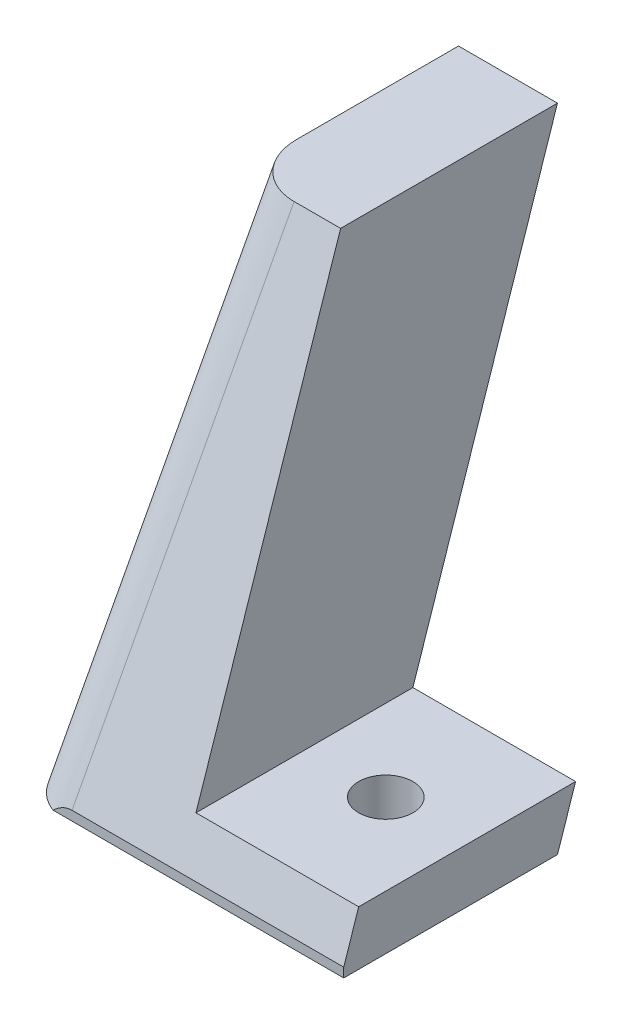
SolidWorks part; units mm, degrees
ref_plane "Спереди" through (0, 0, 0) normal (0, 0, 1) x (1, 0, 0)
ref_plane "Сверху" through (0, 0, 0) normal (0, 1, 0) x (1, 0, 0)
ref_plane "Справа" through (0, 0, 0) normal (1, 0, 0) x (0, 0, -1)
sketch "Эскиз1" plane through (0, 0, 0) normal (0, 1, 0) x (1, 0, 0)
  line L1 (-82.6594, 0) -> (83.4888, 0) construction
  line L3 (-45, 0) -> (-45, 45)
  line L4 (-45, 45) -> (45, 45)
  line L5 (45, 45) -> (45, -45)
  line L6 (45, -45) -> (-45, -45)
  line L7 (-45, -45) -> (-45, 0)
  dimension "D1" = 90
  dimension "D2" = 90
  dimension "D4" = 45
sketch "Эскиз2" plane through (0, 0, 0) normal (0, 0, 1) x (1, 0, 0)
  line L0 (-45, 0) -> (-30, 0)
  line L1 (-30, 0) -> (-30, 45)
  line L2 (45, 0) -> (-45, 0) construction
  line L4 (-45, 0) -> (-30, 0)
  line L5 (0, 0) -> (0, 57.5371) construction
  line L6 (-39.125, 45) -> (-30, 45)
  line L7 (0, 45) -> (-39.125, 45)
  line L8 (-39.125, 45) -> (-45, 0)
  dimension "D1" = 45
  dimension "D2" = 39.125
  dimension "D3" = 82.562
  dimension "D4" = 15
  dimension "D5" = 45
extrude "Бобышка-Вытянуть1" add sketch "Эскиз2" along normal blind 50 contours L6 L8 L0 L1 region at (-36.1505, 20.6736, 0)
sketch "Эскиз4" plane through (0, 0, 0) normal (1, 0, 0) x (0, 0, -1)
  line L0 (-50.289, 0) -> (-50, 45)
  line L2 (-50, 45) -> (-35.289, 45)
  line L3 (-15.2933, 45) -> (-35.289, 45)
  line L4 (-50.289, 0) -> (-35.289, 45)
  line L5 (-50.289, 0) -> (-30.289, 0)
  line L6 (-30.289, 0) -> (-15.2933, 45)
  line L7 (-15.2933, 45) -> (0, 45)
  line L8 (0, 45) -> (0, 0)
  line L9 (0, 0) -> (-30.289, 0)
  dimension "D1" = 71.565
  dimension "D2" = 71.57
  dimension "D3" = 19.9957
  dimension "D4" = 45
  dimension "D5" = 20
  dimension "D6" = 30.289
  dimension "D7" = 50.289
extrude "Вырез-Вытянуть1" cut sketch "Эскиз4" against normal blind 50 contours L7 L8 L9 L6 | L4 L2 L0
sketch "Эскиз7" plane through (-30, 0, 0) normal (1, 0, 0) x (0, 0, -1)
  line L0 (-50, 0) -> (-50, 0.8669)
  line L1 (-50, 0.8669) -> (-48.6223, 5)
  line L2 (-48.6223, 5) -> (-28.6228, 5)
  line L3 (-35.289, 45) -> (-50, 0.8669) construction
  line L4 (-15.2933, 45) -> (-30.289, 0) construction
  line L6 (-28.6228, 5) -> (-30.289, 0)
  line L7 (-30.289, 0) -> (-50, 0)
  dimension "D1" = 5
extrude "Бобышка-Вытянуть3" add sketch "Эскиз7" along normal blind 15
sketch "Эскиз8" plane through (0, 5, 0) normal (0, 1, 0) x (1, 0, 0)
  line L0 (-15, -38.6225) -> (-30, -38.6225) construction
  line L1 (-15, -28.6228) -> (-15, -48.6223) construction
  line L2 (-30, -28.6228) -> (-30, -48.6223) construction
  line L3 (-22.5, -48.6223) -> (-22.5, -28.6228) construction
  line L4 (-15, -48.6223) -> (-30, -48.6223) construction
  line L5 (-15, -28.6228) -> (-30, -28.6228) construction
  circle A0 centre (-22.5, -38.6225) radius 2.5
  dimension "D1" = 5
extrude "Вырез-Вытянуть2" cut sketch "Эскиз8" against normal blind 15 contours A0
fillet "Скругление1" radius 5 1 edges at (-42.0059, 22.9335, 42.6445) type face fillet first side face at (-42.6274, 18.1734, 36.1742) second side face at (-27.752, 20.289, 43.526)
